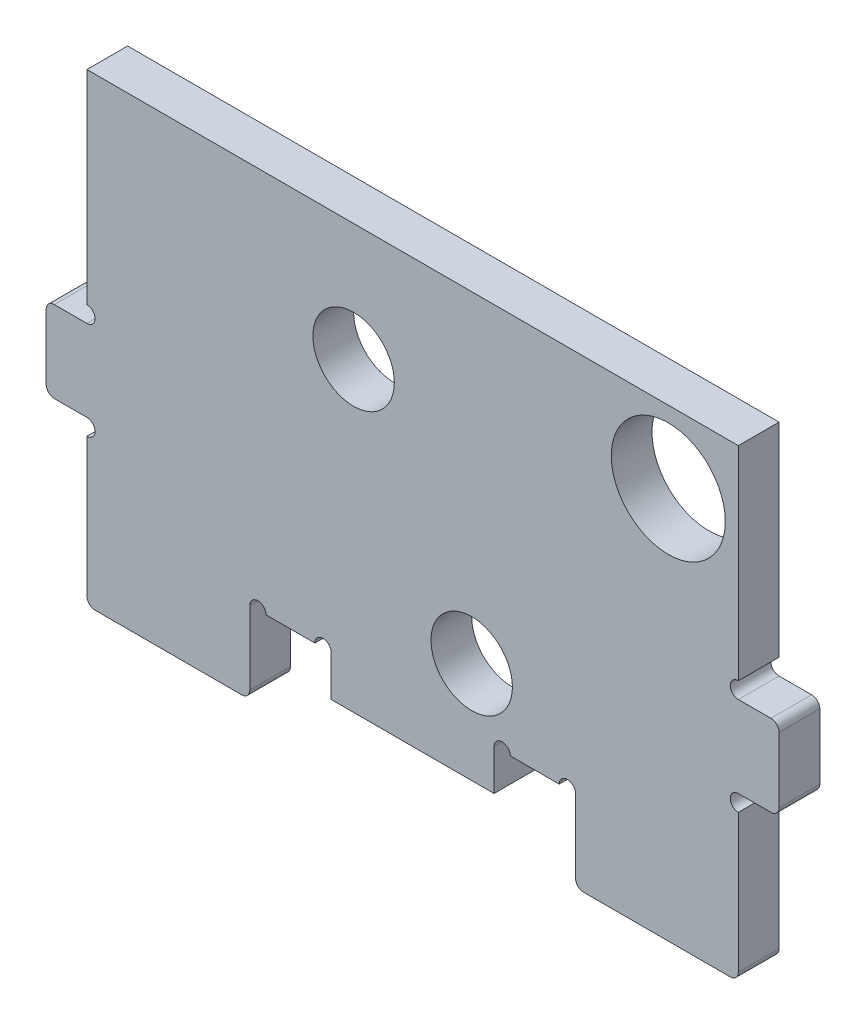
SolidWorks part; units mm, degrees
ref_plane "정면" through (0, 0, 0) normal (0, 0, 1) x (1, 0, 0)
ref_plane "윗면" through (0, 0, 0) normal (0, 1, 0) x (1, 0, 0)
ref_plane "우측면" through (0, 0, 0) normal (1, 0, 0) x (0, 0, -1)
sketch "스케치1" plane through (0, 0, 0) normal (0, 0, 1) x (1, 0, 0)
  line L1 (0, 0) -> (80, 0)
  line L2 (0, 0) -> (0, 52)
  line L3 (0, 52) -> (80, 52)
  line L4 (80, 0) -> (80, 52)
  dimension "D1" = 80
  dimension "D2" = 52
extrude "보스-돌출1" add sketch "스케치1" along normal blind 5
sketch "스케치2" plane through (0, 0, 5) normal (0, 0, 1) x (1, 0, 0)
  line L0 (40, 25) -> (71.3934, 43.125) construction
  line L1 (0, 52) -> (0, 0) construction
  line L3 (0, 0) -> (80, 0) construction
  circle A0 centre (71.3934, 43.125) radius 7
  dimension "D2" = 14
  dimension "D1" = 40
  dimension "D3" = 25
  dimension "D4" = 30
  dimension "D5" = 36.25
extrude "컷-돌출1" cut sketch "스케치2" against normal blind 5
sketch "스케치7" plane through (0, 0, 5) normal (0, 0, 1) x (1, 0, 0)
  line L0 (40, 0) -> (40, 25) construction
  line L1 (0, 0) -> (80, 0) construction
  line L2 (0, 52) -> (0, 0) construction
  line L3 (47.25, 12.4426) -> (40, 25) construction
  line L4 (40, 25) -> (32.75, 37.5574) construction
  circle A0 centre (32.75, 37.5574) radius 5
  circle A1 centre (47.25, 12.4426) radius 5
  dimension "D4" = 10
  dimension "D1" = 40
  dimension "D2" = 25
  dimension "D3" = 30
  dimension "D5" = 29
extrude "컷-돌출4" cut sketch "스케치7" against normal blind 10
sketch "스케치10" plane through (0, 0, 0) normal (0, 0, -1) x (-1, 0, 0)
  line L0 (0, 0) -> (-80, 0) construction
  line L1 (-20, 5) -> (-30, 5)
  line L2 (-20, 5) -> (-20, 0)
  line L3 (-20, 0) -> (-30, 0)
  line L4 (-30, 5) -> (-30, 0)
  line L5 (-30, 5) -> (-30, 0) construction
  line L6 (-50, 5) -> (-50, 0) construction
  line L7 (-50, 0) -> (-60, 0)
  line L8 (-50, 0) -> (-50, 5)
  line L9 (-50, 5) -> (-60, 5)
  line L10 (-60, 0) -> (-60, 5)
extrude "컷-돌출5" cut sketch "스케치10" against normal blind 10
sketch "스케치14" plane through (0, 0, 5) normal (0, 0, 1) x (1, 0, 0)
  line L1 (80, 0) -> (60, 0)
  line L2 (80, 0) -> (80, -5)
  line L3 (80, -5) -> (60, -5)
  line L4 (60, 0) -> (60, -5)
  line L5 (0, 0) -> (20, 0)
  line L6 (0, 0) -> (0, -5)
  line L7 (0, -5) -> (20, -5)
  line L8 (20, 0) -> (20, -5)
  dimension "D1" = 5
extrude "보스-돌출4" add sketch "스케치14" against normal blind 5
sketch "스케치15" plane through (0, 0, 5) normal (0, 0, 1) x (1, 0, 0)
  line L1 (80, -5) -> (80, 52) construction
  line L2 (80, 15) -> (85, 15)
  line L3 (80, 15) -> (80, 25)
  line L4 (80, 25) -> (85, 25)
  line L7 (85, 15) -> (85, 25)
  line L8 (85, 45) -> (85, 25.05) construction
  line L9 (0, 52) -> (0, -5) construction
  line L10 (0, 15) -> (-5, 15)
  line L12 (0, 15) -> (0, 25)
  line L13 (0, 25) -> (-5, 25)
  line L14 (-5, 15) -> (-5, 25)
  line L15 (-5, 45) -> (-5, 25.05) construction
  line L16 (50, 5) -> (60, 5) construction
  dimension "D1" = 10
  dimension "D2" = 10
extrude "보스-돌출5" add sketch "스케치15" against normal blind 5
sketch "스케치11" plane through (0, 0, 5) normal (0, 0, 1) x (1, 0, 0)
  line L0 (50, 5) -> (60, 5) construction
  line L1 (20, 5) -> (30, 5) construction
  line L2 (80, -5) -> (80, 15) construction
  line L3 (80, 25) -> (80, 52) construction
  line L4 (0, 52) -> (0, 25) construction
  circle A0 centre (59, 5) radius 1
  circle A1 centre (51, 5) radius 1
  circle A2 centre (29, 5) radius 1
  circle A3 centre (21, 5) radius 1
  circle A4 centre (80, 14) radius 1
  circle A5 centre (80, 26) radius 1
  circle A6 centre (0, 26) radius 1
  circle A7 centre (0, 14) radius 1
  dimension "D1" = 2
extrude "컷-돌출6" cut sketch "스케치11" against normal blind 10
fillet "필렛2" radius 1 8 edges at (0, -5, 2.5) (20, -5, 2.5) (60, -5, 2.5) (80, -5, 2.5) (85, 25, 2.5) (85, 15, 2.5) (-5, 25, 2.5) (-5, 15, 2.5)
